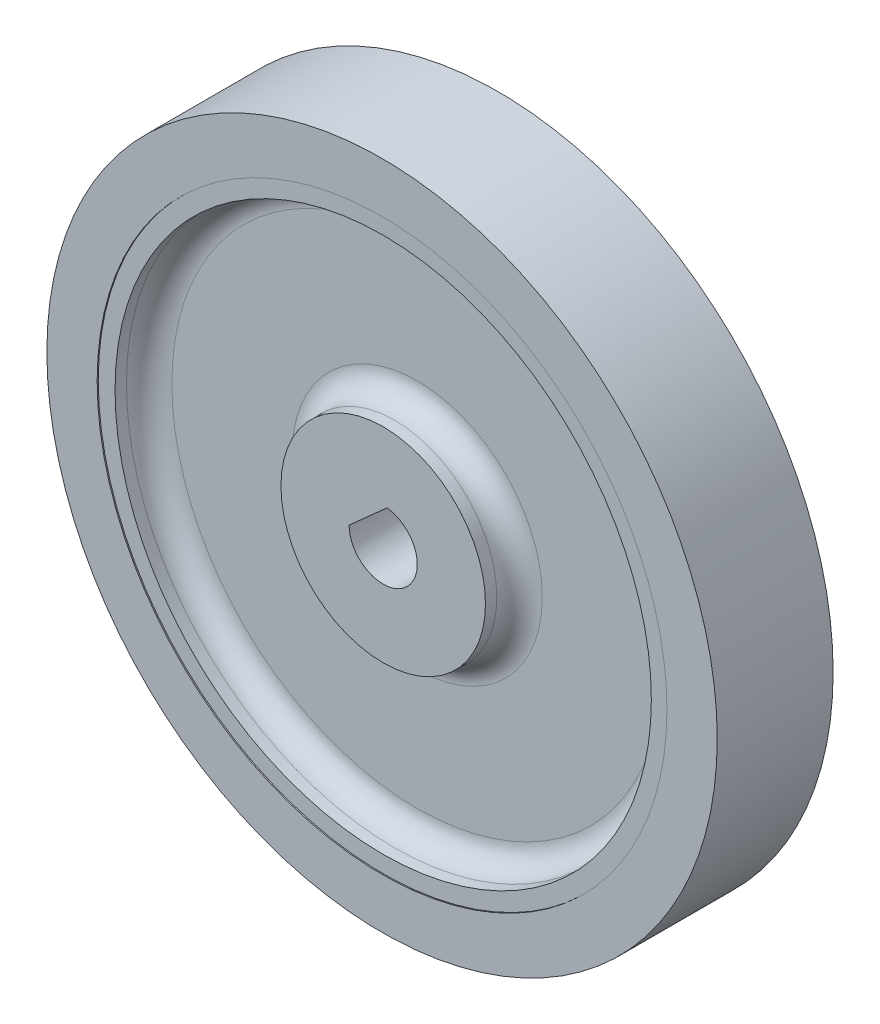
SolidWorks part; units mm, degrees
note: The reader was unsure of these and kept them because the rebuilt part matched: shared geometry of "Esquisse1<3>", "Esquisse1<4>".
material "ABS"
ref_plane "Plan de face" through (0, 0, 0) normal (0, 0, 1) x (1, 0, 0)
ref_plane "Plan de dessus" through (0, 0, 0) normal (0, 1, 0) x (1, 0, 0)
ref_plane "Plan de droite" through (0, 0, 0) normal (1, 0, 0) x (0, 0, -1)
sketch "Esquisse1" plane through (0, 0, 0) normal (0, 0, 1) x (1, 0, 0)
  line L0 (-3, 0) -> (0.3301, 2.9818)
  circle A0 centre (0, 0) radius 29.5
  circle A1 centre (0, 0) radius 23.6
  circle A2 centre (0, 0) radius 9
  arc A3 (-3, 0) -> (0.3301, 2.9818) centre (0, 0) ccw
  circle A4 centre (0, 0) radius 25.075
  dimension "D1" = 59
  dimension "D2" = 6
  dimension "D3" = 18
  dimension "D4" = 47.2
  dimension "D5" = 50.15
  dimension "D6" = 4.47
extrude "Boss.-Extru.1" add sketch "Esquisse1" along normal blind 5 contours A2 A3 L0 | A4 A1
extrude "Boss.-Extru.2" add sketch "Esquisse1<3>" along normal blind 2 contours A1 A2
sketch "Esquisse1<3>" plane through (0, 0, 0) normal (0, 0, 1) x (1, 0, 0) same geometry as "Esquisse1"
extrude "Boss.-Extru.3" add sketch "Esquisse1<4>" along normal blind 5.1 contours A0 A4
sketch "Esquisse1<4>" plane through (0, 0, 0) normal (0, 0, 1) x (1, 0, 0) same geometry as "Esquisse1"
fillet "Congé1" radius 2 2 edges at (23.6, 0, 2) (9, 0, 2)
mirror "Symétrie1" of "Congé1", "Boss.-Extru.2", "Boss.-Extru.3", "Boss.-Extru.1"
equation "\"diametre_roue\"= 59mm"
equation "\"diametre_axe\"= 6mm"
equation "\"D1@Esquisse1\"=\"diametre_roue\""
equation "\"D2@Esquisse1\"=\"diametre_axe\""
equation "\"D3@Esquisse1\"=3*\"D2@Esquisse1\""
equation "\"D4@Esquisse1\"=0.8*\"D1@Esquisse1\""
equation "\"D5@Esquisse1\"=0.85*\"D1@Esquisse1\""
